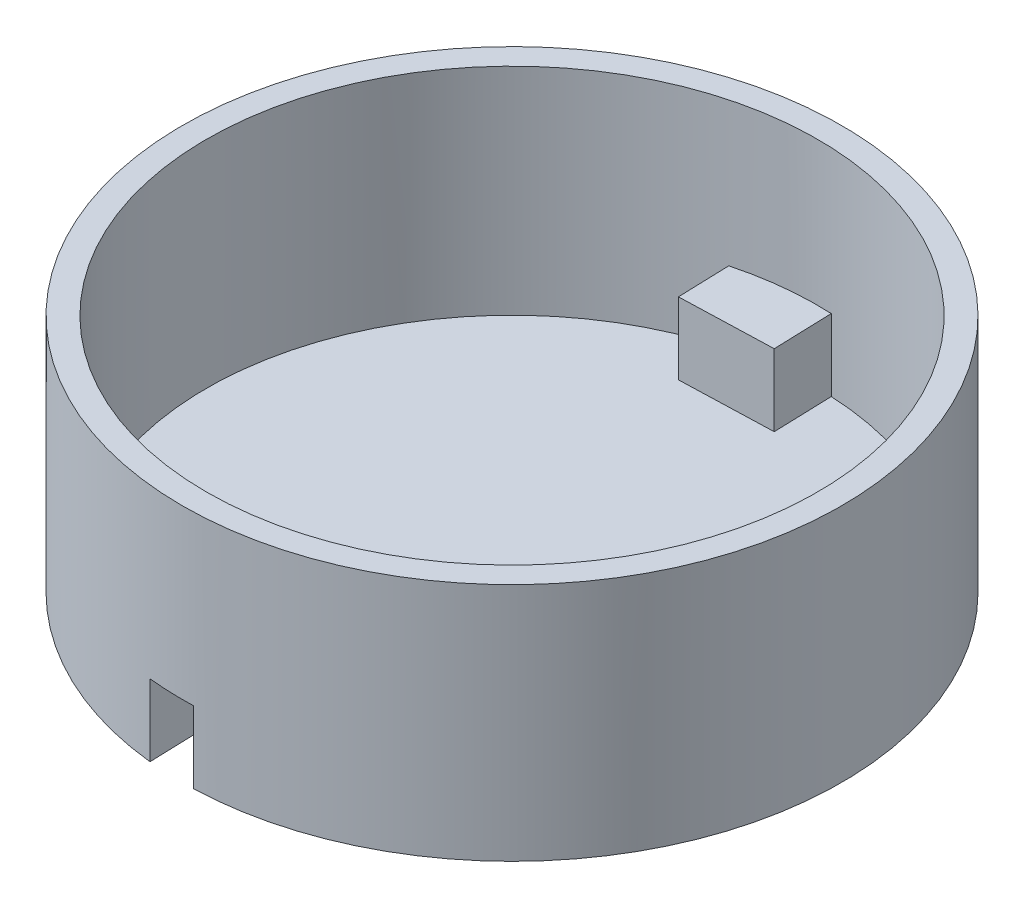
SolidWorks part; units mm, degrees
ref_plane "Alzado" through (0, 0, 0) normal (0, 0, 1) x (1, 0, 0)
ref_plane "Planta" through (0, 0, 0) normal (0, 1, 0) x (1, 0, 0)
ref_plane "Vista lateral" through (0, 0, 0) normal (1, 0, 0) x (0, 0, -1)
sketch "Croquis1" plane through (0, 0, 0) normal (0, 1, 0) x (1, 0, 0)
  circle A0 centre (0, 0) radius 27.5
  dimension "D1" = 55
extrude "Saliente-Extruir1" add sketch "Croquis1" along normal blind 20
sketch "Croquis2" plane through (0, 0, 0) normal (0, -1, 0) x (-1, 0, 0)
  line L0 (3.0163, -22.6101) -> (2.8621, -27.3507)
  line L1 (2.7317, -31.3554) -> (3.0163, -22.6101) construction
  line L2 (3.0163, -22.6101) -> (-0.7317, -22.4881)
  line L3 (-0.7317, -22.4881) -> (-0.8943, -27.4855)
  line L4 (-0.8943, -27.4855) -> (-0.7317, -22.4881) construction
  line L5 (0.7317, 22.4881) -> (4.4797, 22.3661)
  line L6 (4.4797, 22.3661) -> (4.634, 27.1068)
  line L7 (4.7643, 31.1115) -> (4.4797, 22.3661) construction
  line L8 (0.7317, 22.4881) -> (0.8943, 27.4855)
  line L9 (0.8943, 27.4855) -> (0.7317, 22.4881) construction
  arc A0 (-0.8943, -27.4855) -> (2.8621, -27.3507) centre (0, 0) ccw
  circle A1 centre (0, 0) radius 27.5
  arc A2 (4.634, 27.1068) -> (0.8943, 27.4855) centre (0, 0) ccw
  dimension "D1" = 0
extrude "Cortar-Extruir1" cut sketch "Croquis2" against normal blind 6
shell "Vaciado3" thickness 2 removed face at (0, 20, 27.5)
